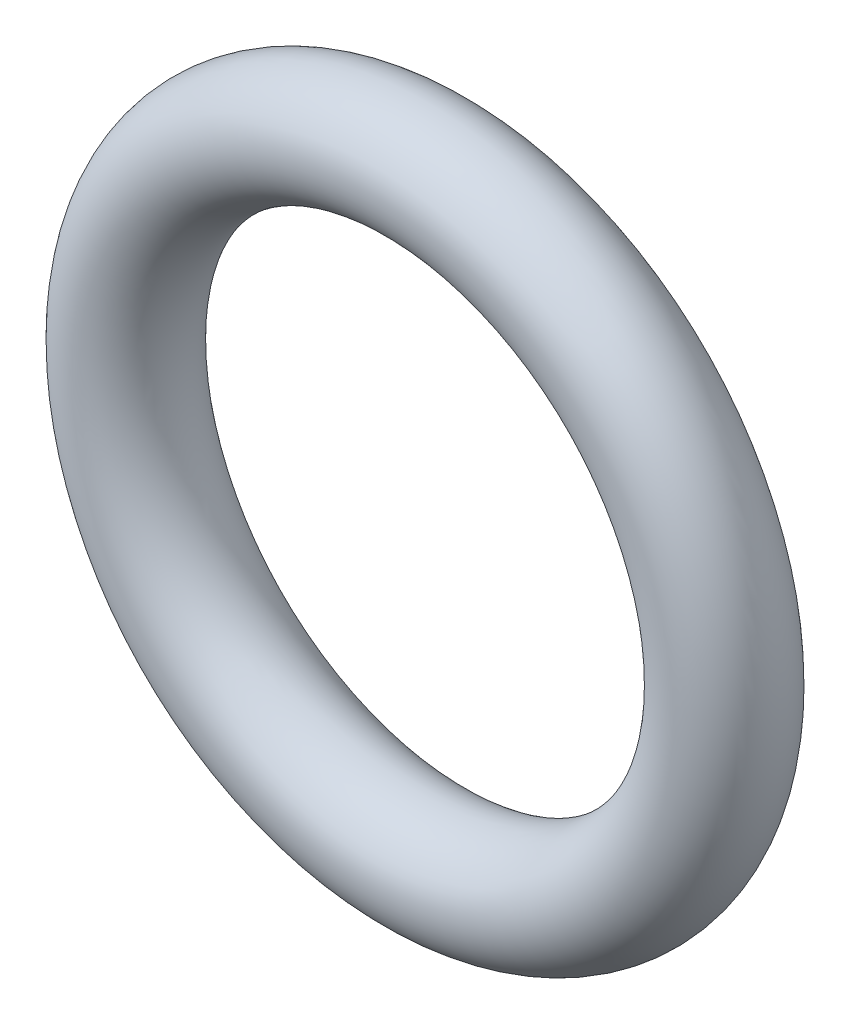
SolidWorks part; units mm, degrees
material "NBR"
ref_plane "Front" through (0, 0, 0) normal (0, 0, 1) x (1, 0, 0)
ref_plane "Top" through (0, 0, 0) normal (0, 1, 0) x (1, 0, 0)
ref_plane "Right" through (0, 0, 0) normal (1, 0, 0) x (0, 0, -1)
ref_axis "Axis1" through (0, 0, -0.9779) along (0, 0, 1)
sketch "Sketch1" plane through (0, 0, 0) normal (1, 0, 0) x (0, -1, 0)
  line L2 (-55, 0) -> (55, 0) construction
  line L3 (-3.8227, 0) -> (3.8227, 0) construction
  circle A0 centre (4.7117, 0) radius 0.889
  point P0 (0, 0)
  point P2 (0, 0)
  point P9 (3.8227, 0)
  dimension "Width" = 1.778
  dimension "ID" = 7.6454
revolve "Revolve1" add sketch "Sketch1" angle 360 about axis through (0, 0, -0.9779) along (0, 0, 1)
